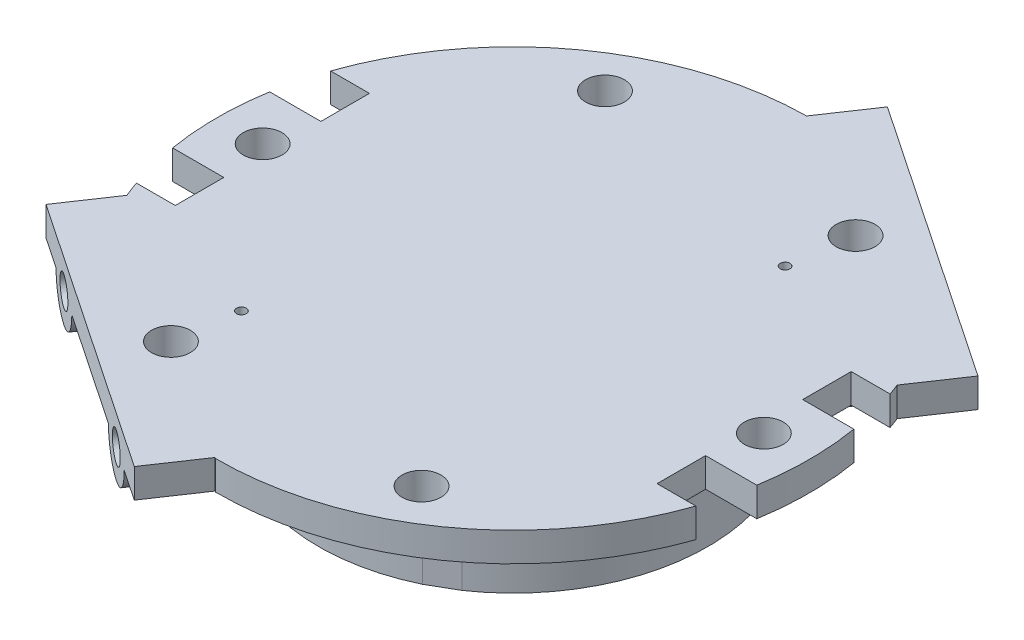
SolidWorks part; units mm, degrees
ref_plane "Alzado" through (0, 0, 0) normal (0, 0, 1) x (1, 0, 0)
ref_plane "Planta" through (0, 0, 0) normal (0, 1, 0) x (1, 0, 0)
ref_plane "Vista lateral" through (0, 0, 0) normal (1, 0, 0) x (0, 0, -1)
sketch "Croquis1" plane through (0, 0, 0) normal (0, 1, 0) x (1, 0, 0)
  circle A0 centre (0, 0) radius 30.5
extrude "Saliente-Extruir1" add sketch "Croquis1" along normal blind 3
sketch "Croquis5" plane through (0, 3, 0) normal (0, 1, 0) x (1, 0, 0)
  line L1 (28.8141, -5) -> (30.0874, -5)
  line L2 (28.8141, 5) -> (30.0874, 5)
  line L3 (-24.8141, 10) -> (-28.8141, 10)
  line L4 (24.8141, -5) -> (24.8141, -10)
  line L5 (-24.8141, -10) -> (-28.8141, -10)
  line L6 (24.8141, -5) -> (28.8141, -5)
  line L7 (24.8141, 5) -> (24.8141, 10)
  line L8 (-24.8141, 5) -> (-28.8141, 5)
  line L9 (-24.8141, 5) -> (-24.8141, 10)
  line L10 (-24.8141, -5) -> (-28.8141, -5)
  line L11 (-24.8141, -5) -> (-24.8141, -10)
  line L12 (24.8141, 5) -> (28.8141, 5)
  line L13 (24.8141, -10) -> (28.8141, -10)
  line L14 (24.8141, 10) -> (28.8141, 10)
  line L15 (-28.8141, 5) -> (-30.0874, 5)
  line L16 (-28.8141, -5) -> (-30.0874, -5)
  line L18 (-24.8141, 0) -> (-12.407, -21.4896)
  line L19 (-12.407, -21.4896) -> (12.407, -21.4896)
  line L20 (12.407, -21.4896) -> (24.8141, 0)
  line L21 (24.8141, 0) -> (12.407, 21.4896)
  line L22 (12.407, 21.4896) -> (-12.407, 21.4896)
  line L23 (-12.407, 21.4896) -> (-24.8141, 0)
  circle A0 centre (0, 0) radius 21.4896 construction
  circle A1 centre (0, 0) radius 30.5 construction
  arc A2 (-28.8141, 10) -> (-30.0874, 5) centre (0, 0) ccw
  arc A4 (-30.0874, -5) -> (-28.8141, -10) centre (0, 0) ccw
  arc A5 (30.0874, -5) -> (28.8141, -10) centre (0, 0) cw
  arc A6 (28.8141, 10) -> (30.0874, 5) centre (0, 0) cw
  circle M2 centre (0, 0) radius 30.5
extrude "Cortar-Extruir3" cut sketch "Croquis5" against normal blind 4 contours L10 L16 L5 L11 M2 | L15 L8 L9 L3 M2 | L14 L7 L12 L2 M2 | L4 L13 L1 L6 M2 region at (27.1844, 3, 7.3876) region at (-27.1844, 3, 7.3876) region at (27.1844, 3, -7.3876) region at (-27.1844, 3, -7.3876)
sketch "Croquis7" plane through (0, 3, 0) normal (0, 1, 0) x (1, 0, 0)
  line L2 (25.8141, 0) -> (12.907, 22.3556)
  line L3 (12.907, 22.3556) -> (-12.907, 22.3556)
  line L4 (-12.907, 22.3556) -> (-25.8141, 0)
  line L5 (-25.8141, 0) -> (-12.907, -22.3556)
  line L6 (-12.907, -22.3556) -> (12.907, -22.3556)
  line L7 (12.907, -22.3556) -> (25.8141, 0)
  circle A0 centre (25.8141, 0) radius 2
  circle A4 centre (-25.8141, 0) radius 2
  circle A5 centre (0, 0) radius 22.3556 construction
  circle A6 centre (12.907, 22.3556) radius 2
  circle A7 centre (-12.907, -22.3556) radius 2
  circle A8 centre (-12.907, 22.3556) radius 2
  circle A9 centre (12.907, -22.3556) radius 2
extrude "Cortar-Extruir4" cut sketch "Croquis7" against normal blind 10 contours A8 L4 L3 | A4 L4 L5 | A4 L5 L4 | A8 L3 L4 | L2 A6 L3 | L3 A6 L2 | L7 A0 L2 | L2 A0 L7 | A7 L5 L6 | A7 L6 L5 | L6 A9 L7 | L7 A9 L6 | A4 region at (24.7114, 3, 0) region at (26.3654, 3, 0) region at (12.3557, 3, -21.4007) region at (13.1827, 3, -22.8331) region at (13.1827, 3, 22.8331) region at (12.3557, 3, 21.4007) region at (-12.3557, 3, -21.4007) region at (-13.1827, 3, -22.8331) region at (-13.1827, 3, 22.8331) region at (-12.3557, 3, 21.4007) region at (-24.7114, 3, 0) region at (-26.3654, 3, 0)
sketch "Croquis8" plane through (0, 3, 0) normal (0, 1, 0) x (1, 0, 0)
  line L0 (0, 0) -> (12, 0)
  line L1 (12, 0) -> (12, 16)
  line L2 (0, 0) -> (-12, 0)
  line L3 (-12, 0) -> (-12, -16)
  circle A0 centre (12, 16) radius 0.5
  circle A1 centre (-12, -16) radius 0.5
extrude "Cortar-Extruir5" cut sketch "Croquis8" against normal blind 3 contours A1 | A0 region at (11.6564, 3, -16.3436) region at (-11.6564, 3, 15.6564)
sketch "Croquis9" plane through (0, 3, 0) normal (0, 1, 0) x (1, 0, 0)
  line L2 (-10, 17.3205) -> (-8.701, 18.0705)
  line L5 (25.6318, 16.5306) -> (27.1318, 13.9325)
  line L6 (-10, 17.3205) -> (-11.299, 16.5705)
  line L8 (10, -17.3205) -> (8.701, -18.0705)
  line L9 (10, -17.3205) -> (11.299, -16.5705)
  circle A0 centre (0, 0) radius 20.0562
  circle A1 centre (-12, -16) radius 3
  circle A2 centre (12, 16) radius 3
extrude "Saliente-Extruir2" add sketch "Croquis9" against normal blind 13 contours L2 L6 | L8 L9 region at (0, 3, 0)
sketch "Croquis10" plane through (0, 3, 0) normal (0, 1, 0) x (1, 0, 0)
  line L3 (29.8013, 10.2046) -> (-1.7022, 31.454)
  circle A0 centre (0, 0) radius 31.5
extrude "Cortar-Extruir6" cut sketch "Croquis10" against normal blind 3 contours L3 A0 rebuild error yes
sketch "Croquis11" plane through (14.0495, 0, -20.8293) normal (0.5592, 0, -0.829) x (-0.829, 0, -0.5592)
  line L1 (17.2916, 0) -> (-17.2916, 0)
  line L2 (17.2916, 0) -> (17.2916, 3)
  line L3 (17.2916, 3) -> (-17.2916, 3)
  line L4 (-17.2916, 0) -> (-17.2916, 3)
extrude "Saliente-Extruir3" add sketch "Croquis11" along normal blind 6
sketch "Croquis12" plane through (0, 3, 0) normal (0, 1, 0) x (1, 0, 0)
  circle A0 centre (12.907, 22.3556) radius 2
extrude "Cortar-Extruir7" cut sketch "Croquis12" against normal blind 3
sketch "Croquis13" plane through (17.4047, 0, -25.8035) normal (0.5592, 0, -0.829) x (-0.829, 0, -0.5592)
  line L0 (-17.2916, 0) -> (17.2916, 0)
  line L1 (17.2916, 3) -> (-17.2916, 3)
  line L2 (17.2916, 3) -> (-17.2916, 3) construction
  line L3 (17.2916, 0) -> (17.2916, 3) construction
  circle A1 centre (10, 0) radius 3
  circle A2 centre (-10, 0) radius 3
  circle A3 centre (10, 0) radius 1.5
  circle A5 centre (-10, 0) radius 1.5
  line M4 (-17.2916, 0) -> (17.2916, 0)
extrude "Saliente-Extruir4" add sketch "Croquis13" against normal blind 20 contours A3 L0 A1 | A3 L0 A1 | A5 L0 A2 | A5 L0 A2 | A5 M4 | A3 M4 region at (25.6951, 1.5671, -20.2116) region at (25.6951, -0.6366, -20.2116) region at (23.8297, -0.0671, -21.4698) region at (10.8337, 2.0739, -30.2358) region at (10.9797, -0.0671, -30.1373) region at (9.1143, -0.6366, -31.3955)
sketch "Croquis14" plane through (17.4047, 0, -25.8035) normal (0.5592, 0, -0.829) x (-0.829, 0, -0.5592)
  circle A0 centre (-10, 0) radius 1.5
  circle A1 centre (10, 0) radius 1.5
extrude "Cortar-Extruir8" cut sketch "Croquis14" against normal blind 6
sketch "Croquis15" plane through (0, 3, 0) normal (0, 1, 0) x (1, 0, 0)
  line L0 (28.3849, 11.16) -> (-0.2859, 30.4987)
  line L1 (28.3849, 11.16) -> (0.1409, -30.7136)
  line L2 (-0.2859, 30.4987) -> (-28.5299, -11.3749)
  line L3 (0.1409, -30.7136) -> (-28.5299, -11.3749)
  circle A0 centre (-0.2859, 0) radius 30.7165
  arc M12 (-28.8141, -10) -> (28.8141, -10) centre (0, 0) ccw
  circle M28 centre (-12.907, -22.3556) radius 2
extrude "Cortar-Extruir9" cut sketch "Croquis15" against normal blind 3 contours L3 M12 M28 region at (-15.494, 3, 22.7434)
sketch "Croquis16" plane through (-14.1945, 0, 21.0442) normal (-0.5592, 0, 0.829) x (0.829, 0, 0.5592)
  line L0 (-16.9088, 0) -> (-16.9088, 3)
  line L1 (-16.9088, 0) -> (16.78, 0)
  line L2 (-16.9088, 3) -> (16.78, 3)
  line L3 (16.78, 0) -> (16.78, 3)
extrude "Saliente-Extruir5" add sketch "Croquis16" along normal blind 6
sketch "Croquis17" plane through (0, 3, 0) normal (0, 1, 0) x (1, 0, 0)
  circle A0 centre (-12.907, -22.3556) radius 2
extrude "Cortar-Extruir10" cut sketch "Croquis17" against normal blind 3
sketch "Croquis18" plane through (-17.5497, 0, 26.0185) normal (-0.5592, 0, 0.829) x (0.829, 0, 0.5592)
  line L2 (-16.9088, 0) -> (16.78, 0) construction
  circle A0 centre (9.9356, 0) radius 3
  circle A1 centre (-10.0644, 0) radius 3
extrude "Saliente-Extruir6" add sketch "Croquis18" against normal blind 25
sketch "Croquis19" plane through (-17.5497, 0, 26.0185) normal (-0.5592, 0, 0.829) x (0.829, 0, 0.5592)
  circle A0 centre (-10.0644, 0) radius 1.5
  circle A1 centre (9.9356, 0) radius 1.5
extrude "Cortar-Extruir11" cut sketch "Croquis19" against normal blind 5
